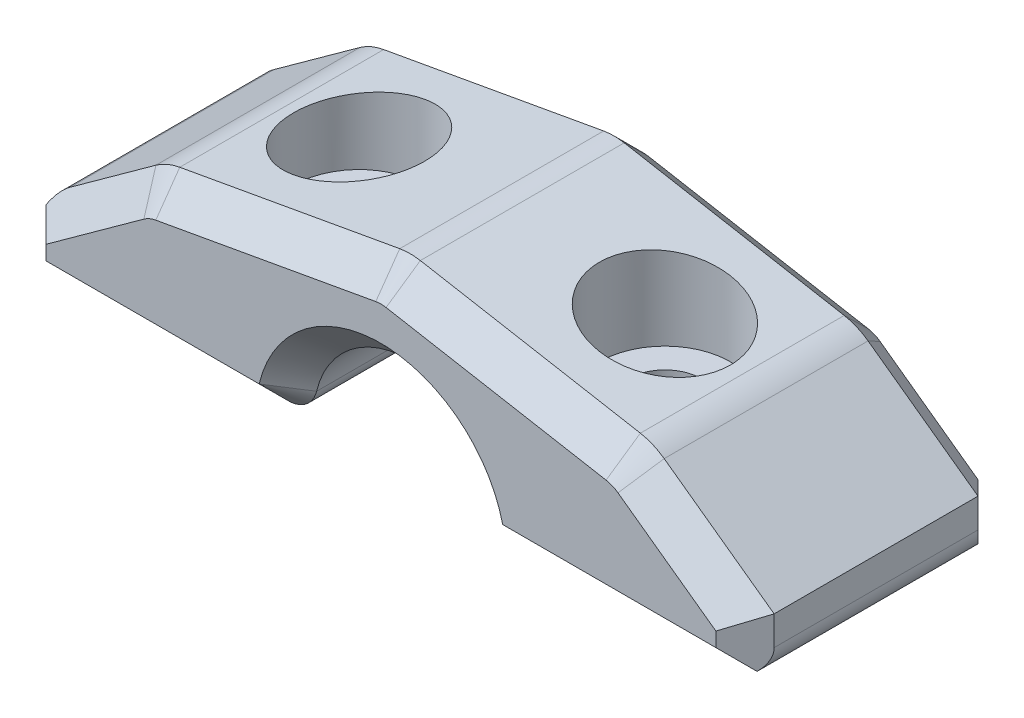
SolidWorks part; units mm, degrees
ref_plane "Front Plane" through (0, 0, 0) normal (0, 0, 1) x (1, 0, 0)
ref_plane "Top Plane" through (0, 0, 0) normal (0, 1, 0) x (1, 0, 0)
ref_plane "Right Plane" through (0, 0, 0) normal (1, 0, 0) x (0, 0, -1)
sketch "Sketch1" plane through (0, 0, 0) normal (0, 0, 1) x (1, 0, 0)
  line L0 (-3.3, 0) -> (-12.5, 0)
  line L1 (-12.5, 0) -> (-12.5, 6.5)
  line L2 (-12.5, 6.5) -> (12.5, 6.5)
  line L3 (0, 6.5) -> (0, 3.3) construction
  line L4 (12.5, 0) -> (12.5, 6.5)
  line L5 (3.3, 0) -> (12.5, 0)
  arc A0 (3.3, 0) -> (-3.3, 0) centre (0, 0) ccw
  dimension "D1" = 6.6
  dimension "D2" = 25
  dimension "D3" = 6.5
extrude "Boss-Extrude1" add sketch "Sketch1" along normal blind 9
sketch "Sketch2" plane through (0, 0, 9) normal (0, 0, 1) x (1, 0, 0)
  line L0 (0, 6.5) -> (-8.3557, 5)
  line L1 (12.5, 6.5) -> (-12.5, 6.5) construction
  line L2 (-8.3557, 5) -> (-12.5, 2.0044)
  line L3 (-12.5, 6.5) -> (-12.5, 0) construction
  line L4 (-12.5, 2.0044) -> (-12.5, 6.5)
  line L5 (-12.5, 6.5) -> (12.5, 6.5)
  line L6 (0, 8.1862) -> (0, -3.9101) construction
  line L7 (12.5, 2.0044) -> (12.5, 6.5)
  line L8 (8.3557, 5) -> (12.5, 2.0044)
  line L9 (0, 6.5) -> (8.3557, 5)
  line L10 (-12.5, 0) -> (-3.3, 0) construction
  line M8 (12.5, 0) -> (12.5, 6.5)
  line M9 (12.5, 6.5) -> (-12.5, 6.5)
  line M10 (-12.5, 6.5) -> (-12.5, 0)
  dimension "D1" = 5
  dimension "D2" = 16.7114
  dimension "D3" = 4.4956
extrude "Cut-Extrude1" cut sketch "Sketch2" against normal through all both and the other way through all contours L2 L0 M9 M10 | L9 L8 M9 M8 region at (-9.0286, 5.2531, 9) region at (9.0286, 5.2531, 9)
chamfer "Chamfer1" distance 1 angle 45 4 edges at (-12.5, 1.0022, 0) (12.5, 1.0022, 0) (12.5, 1.0022, 9) (-12.5, 1.0022, 9)
fillet "Fillet3" radius 1 4 edges at (12.5, 0, 4.5) (3.3, 0, 4.5) (-12.5, 0, 4.5) (-3.3, 0, 4.5)
sketch "Sketch4" plane through (0, 0, 0) normal (0, -1, 0) x (1, 0, 0)
  line L0 (0, 9) -> (0, 0) construction
  line L1 (-5.25, 4.5) -> (5.25, 4.5) construction
  line L2 (3.2095, 9) -> (-3.2095, 9) construction
  line L4 (-3.2095, 0) -> (3.2095, 0) construction
  circle A0 centre (-5.25, 4.5) radius 1.25
  circle A1 centre (5.25, 4.5) radius 1.25
  point P8 (0, 4.5)
  point P17 (0, 4.5)
  dimension "D2" = 2.5
  dimension "D1" = 10.5
extrude "Cut-Extrude2" cut sketch "Sketch4" against normal through all
sketch "Sketch5" plane through (0, 0, 0) normal (0, 1, 0) x (1, 0, 0)
  circle A0 centre (-5.25, -4.5) radius 2.25
  circle A1 centre (5.25, -4.5) radius 2.25
  dimension "D1" = 4.5
extrude "Cut-Extrude3" cut sketch "Sketch5" along normal blind 10 from offset 3
fillet "Fillet2" radius 2 4 edges at (8.3557, 5, 4.5) (-8.3557, 5, 4.5) (0, 6.5, 4.5) (-12.5, 2.0044, 4.5)
chamfer "Chamfer2" distance 1 angle 45 12 edges at (-10.1126, 3.7301, 0) (-8.3356, 4.9528, 0) (-4.1302, 5.7586, 0) (10.1126, 3.7301, 0) (0, 6.468, 0) (8.3356, 4.9528, 0) (4.1302, 5.7586, 0) (0, 3.3, 0) (-7.8411, 0, 0) (7.8411, 0, 0) (-3.5627, 0.215, 0) (3.5627, 0.215, 0)
chamfer "Chamfer3" distance 1 angle 45 12 edges at (-10.1126, 3.7301, 9) (-7.8411, 0, 9) (-3.5627, 0.215, 9) (0, 3.3, 9) (3.5627, 0.215, 9) (7.8411, 0, 9) (-8.3356, 4.9528, 9) (-4.1302, 5.7586, 9) (10.1126, 3.7301, 9) (0, 6.468, 9) (8.3356, 4.9528, 9) (4.1302, 5.7586, 9)
